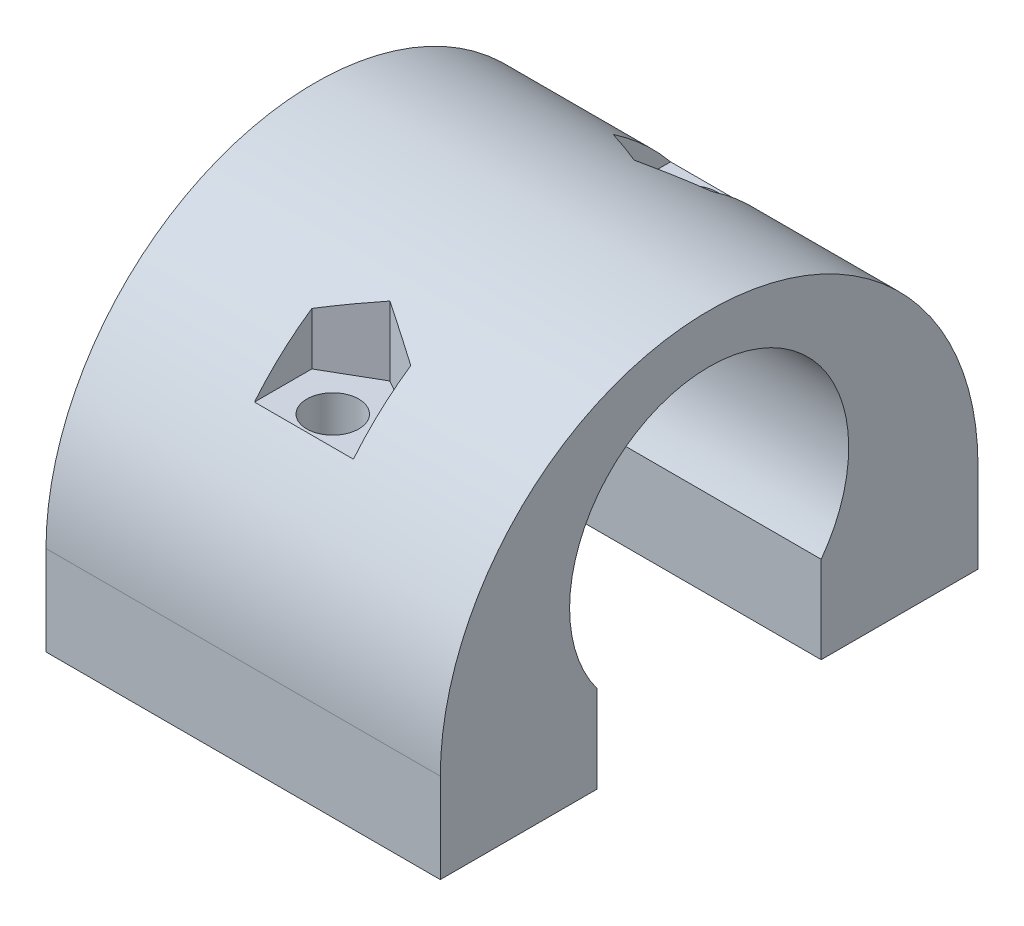
SolidWorks part; units mm, degrees
ref_plane "Front Plane" through (0, 0, 0) normal (0, 0, 1) x (1, 0, 0)
ref_plane "Top Plane" through (0, 0, 0) normal (0, 1, 0) x (1, 0, 0)
ref_plane "Right Plane" through (0, 0, 0) normal (1, 0, 0) x (0, 0, -1)
sketch "Sketch1" plane through (0, 0, 0) normal (0, 1, 0) x (1, 0, 0)
  line L1 (-21.0811, 11.7568) -> (0.9189, 11.7568)
  line L2 (-21.0811, 11.7568) -> (-21.0811, -18.2432)
  line L3 (-21.0811, -18.2432) -> (0.9189, -18.2432)
  line L4 (0.9189, 11.7568) -> (0.9189, -18.2432)
  dimension "D1" = 30
  dimension "D2" = 22
extrude "Boss-Extrude1" add sketch "Sketch1" along normal blind 20
fillet "Fillet2" 2 edges at (-10.0811, 20, -11.7568) (-10.0811, 20, 18.2432) type full round first side face at (-10.0811, 10, -11.7568) second side face at (-10.0811, 10, 18.2432) middle face at (-10.0811, 20, 3.2432)
sketch "Sketch7" plane through (0, 0, 0) normal (0, -1, 0) x (1, 0, 0)
  line L1 (-21.0811, -11.7568) -> (0.9189, -11.7568)
  line L2 (-21.0811, -11.7568) -> (-21.0811, -3.4568)
  line L3 (-21.0811, -3.4568) -> (0.9189, -3.4568)
  line L4 (0.9189, -11.7568) -> (0.9189, -3.4568)
  line L8 (-21.0811, 9.9432) -> (0.9189, 9.9432)
  line L9 (-21.0811, 9.9432) -> (-21.0811, 18.2432)
  line L10 (-21.0811, 18.2432) -> (0.9189, 18.2432)
  line L11 (0.9189, 9.9432) -> (0.9189, 18.2432)
  line L15 (-21.0811, -11.7568) -> (-21.0811, 18.2432) construction
  line L16 (0.9189, 18.2432) -> (0.9189, -11.7568) construction
  dimension "D1" = 8.3
  dimension "D2" = 8.3
extrude "Boss-Extrude2" add sketch "Sketch7" against normal blind 3.988
sketch "Sketch4" plane through (0, 0, 0) normal (0, -1, 0) x (-1, 0, 0)
  line L1 (-0.9189, -18.2432) -> (-0.9189, 11.7568) construction
  line L3 (-0.9189, -18.2432) -> (-0.9189, 11.7568) construction
  line L6 (21.0811, -18.2432) -> (-0.9189, -18.2432) construction
  circle A0 centre (10.0811, 6.7568) radius 1.45
  circle A1 centre (10.0811, -13.2432) radius 1.45
  dimension "D1" = 20
  dimension "D3" = 5
  dimension "D4" = 2.9
  dimension "D5" = 2.9
  dimension "D2" = 11
  dimension "D6" = 11
sketch "Sketch3" plane through (-21.0811, 0, 0) normal (-1, 0, 0) x (0, 0, 1)
  line L2 (18.2432, 5) -> (18.2432, 0) construction
  circle A0 centre (3.2432, 9.5) radius 7.7866
  arc A1 (18.2432, 5) -> (-11.7568, 5) centre (3.2432, 5) ccw construction
  dimension "D2" = 4.5
  dimension "D1" = 15
extrude "Cut-Extrude2" cut sketch "Sketch3" against normal blind 25
extrude "Cut-Extrude3" cut sketch "Sketch4" against normal blind 19
sketch "Sketch9" plane through (0, 0, 0) normal (0, -1, 0) x (1, 0, 0)
  line L1 (-21.0811, -3.0068) -> (0.9189, -3.0068)
  line L2 (-21.0811, -3.0068) -> (-21.0811, 9.4932)
  line L3 (-21.0811, 9.4932) -> (0.9189, 9.4932)
  line L4 (0.9189, -3.0068) -> (0.9189, 9.4932)
  line L5 (0.9189, -11.7568) -> (-21.0811, -11.7568) construction
  line L7 (-21.0811, -11.7568) -> (-21.0811, 18.2432) construction
  dimension "D1" = 12.5
  dimension "D2" = 8.75
  dimension "D3" = 22
extrude "Cut-Extrude5" cut sketch "Sketch9" against normal blind 5
ref_plane "Plane1" through (0, 15, 0) normal (0, -1, 0) x (-1, 0, 0)
ref_plane "Plane2" through (0, 20, 0) normal (0, -1, 0) x (-1, 0, 0)
sketch "Sketch10" plane through (0, 20, 0) normal (0, -1, 0) x (-1, 0, 0)
  line L13 (10.0811, -13.2432) -> (10.0811, -10.0563) construction
  line L14 (7.3211, -14.8367) -> (10.0811, -16.4302)
  line L15 (10.0811, -16.4302) -> (12.8411, -14.8367)
  line L16 (12.8411, -14.8367) -> (12.8411, -11.6498)
  line L17 (12.8411, -11.6498) -> (10.0811, -10.0563)
  line L18 (10.0811, -10.0563) -> (7.3211, -11.6498)
  line L19 (7.3211, -11.6498) -> (7.3211, -14.8367)
  line L20 (7.3211, 5.1633) -> (10.0811, 3.5698)
  line L21 (10.0811, 3.5698) -> (12.8411, 5.1633)
  line L22 (12.8411, 5.1633) -> (12.8411, 8.3502)
  line L23 (12.8411, 8.3502) -> (10.0811, 9.9437)
  line L24 (10.0811, 9.9437) -> (7.3211, 8.3502)
  line L25 (7.3211, 8.3502) -> (7.3211, 5.1633)
  circle A0 centre (10.0811, -13.2432) radius 2.76 construction
  circle A1 centre (10.0811, 6.7568) radius 2.76 construction
  circle A2 centre (10.0811, -13.2432) radius 0.5304 construction
  point P0 (7.3211, -13.2432)
  dimension "D1" = 5.52
  dimension "D2" = 5.52
extrude "Cut-Extrude6" cut sketch "Sketch10" along normal blind 5.5
